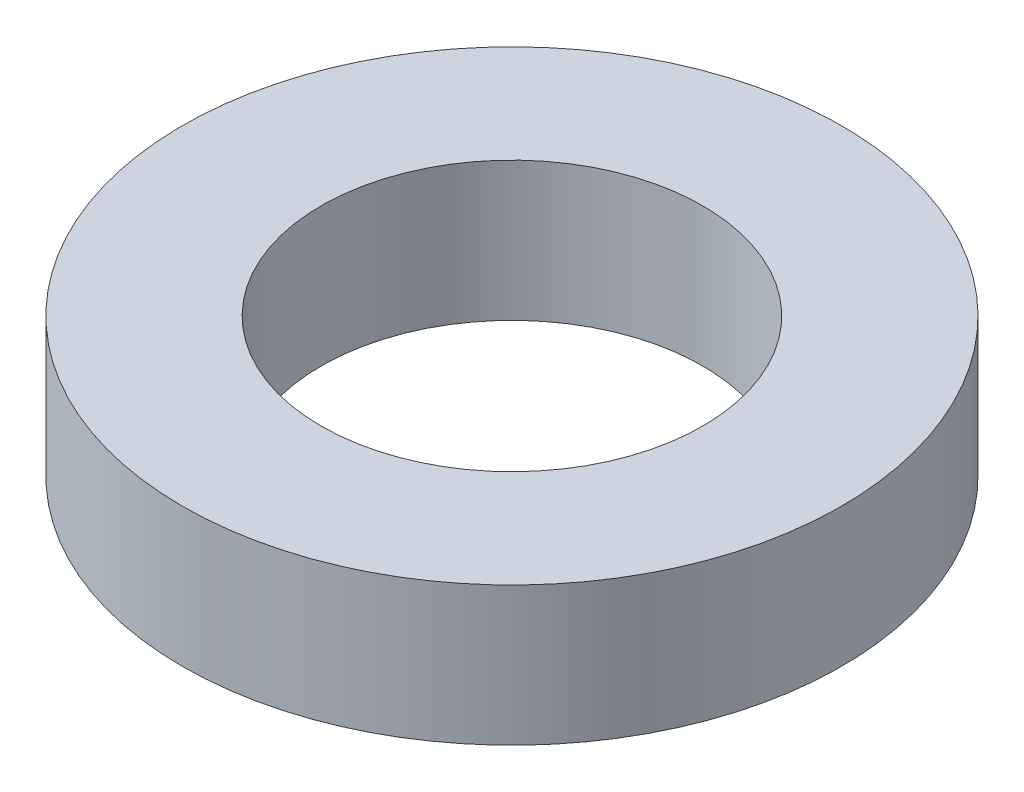
SolidWorks part; units mm, degrees
ref_plane "Front Plane" through (0, 0, 0) normal (0, 0, 1) x (1, 0, 0)
ref_plane "Top Plane" through (0, 0, 0) normal (0, 1, 0) x (1, 0, 0)
ref_plane "Right Plane" through (0, 0, 0) normal (1, 0, 0) x (0, 0, -1)
sketch "Sketch1" plane through (0, 0, 0) normal (0, 1, 0) x (1, 0, 0)
  circle A0 centre (0, 0) radius 47.5
  dimension "FLANGE_OD" = 95
extrude "Boss-Extrude1" add sketch "Sketch1" along normal blind 20
sketch "Sketch2" plane through (0, 0, 0) normal (0, 1, 0) x (1, 0, 0)
  circle A0 centre (0, 0) radius 27.5
  dimension "BORE_D" = 55
extrude "Cut-Extrude1" cut sketch "Sketch2" along normal through all
sketch "Sketch3" plane through (0, 20, 0) normal (0, 1, 0) x (1, 0, 0)
  circle A0 centre (0, 0) radius 17.8405 construction
  circle A1 centre (-17.8405, 0) radius 1.8517
  dimension "BOLT_D" = 3.7034
  dimension "BOLT_PCD" = 35.681
extrude "Cut-Extrude2" cut sketch "Sketch3" against normal blind 17.4371 rebuild error yes
pattern_circular "CirPattern1" count 4 over 360 rebuild error yes
